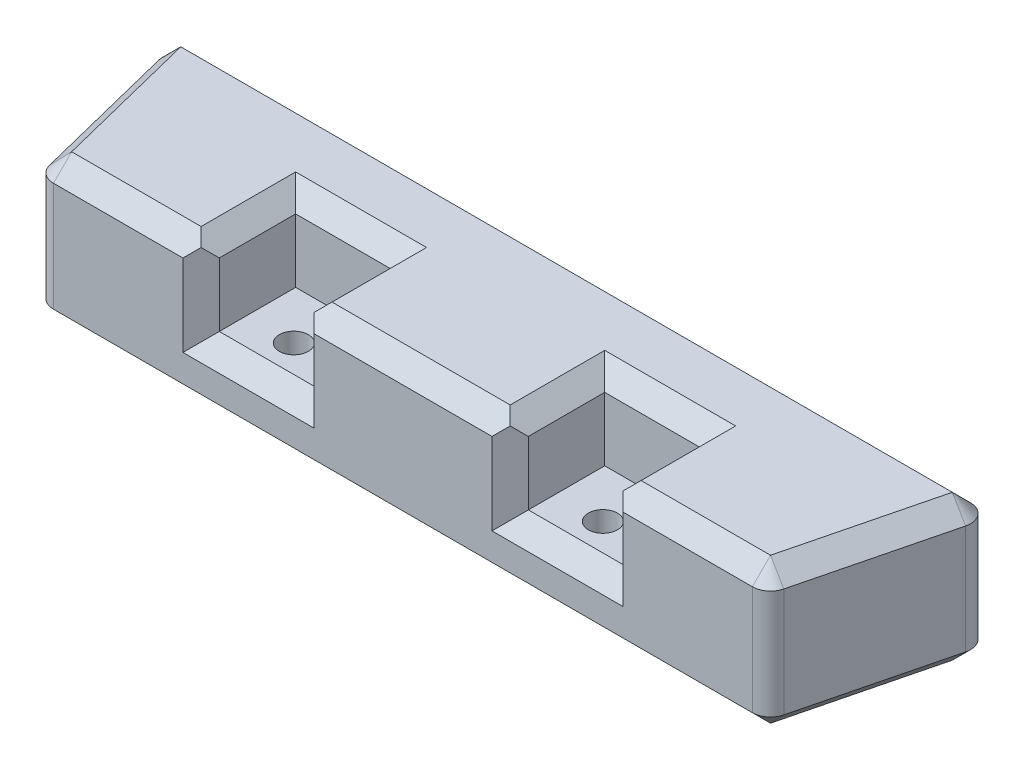
SolidWorks part; units mm, degrees
material "Liga 1060"
ref_plane "Plano frontal" through (0, 0, 0) normal (0, 0, 1) x (1, 0, 0)
ref_plane "Plano superior" through (0, 0, 0) normal (0, 1, 0) x (1, 0, 0)
ref_plane "Plano direito" through (0, 0, 0) normal (1, 0, 0) x (0, 0, -1)
sketch "Esboço2" plane through (0, 0, 0) normal (0, 1, 0) x (1, 0, 0)
  line L4 (-0.1894, 0.7575) -> (-2.1894, 8.7575)
  line L6 (42.1894, 8.7575) -> (40.1894, 0.7575)
  line L7 (39.2192, 0) -> (0.7808, 0)
  line L8 (-1.2192, 10) -> (41.2192, 10)
  arc A1 (40.1894, 0.7575) -> (39.2192, 0) centre (39.2192, 1) cw
  arc A2 (-0.1894, 0.7575) -> (0.7808, 0) centre (0.7808, 1) ccw
  arc A5 (42.1894, 8.7575) -> (41.2192, 10) centre (41.2192, 9) ccw
  arc A6 (-2.1894, 8.7575) -> (-1.2192, 10) centre (-1.2192, 9) cw
  point P2 (20, 10)
  point P6 (20, 0)
  point P7 (42.5, 10)
  point P10 (40, 0)
  point P13 (0, 0)
  point P18 (-2.5, 10)
  dimension "D4" = 1
  dimension "D5" = 45
  dimension "D2" = 10
  dimension "D3" = 1
  dimension "D1" = 40
extrude "Ressalto-extrusão2" add sketch "Esboço2" along normal blind 8
sketch "Esboço4" plane through (0, 8, 0) normal (0, 1, 0) x (1, 0, 0)
  line L0 (20, 0) -> (20, 2.6) construction
  line L1 (0.7808, 0) -> (39.2192, 0) construction
  line L2 (11.5, 2.6) -> (28.5, 2.6) construction
  line L4 (25.9, 0) -> (31.1, 0)
  line L5 (25.9, 0) -> (25.9, 5.2)
  line L6 (25.9, 5.2) -> (31.1, 5.2)
  line L7 (31.1, 0) -> (31.1, 5.2)
  line L8 (25.9, 0) -> (31.1, 5.2) construction
  line L9 (25.9, 5.2) -> (31.1, 0) construction
  line L10 (14.1, 0) -> (8.9, 0)
  line L11 (14.1, 0) -> (14.1, 5.2)
  line L12 (14.1, 5.2) -> (8.9, 5.2)
  line L13 (8.9, 0) -> (8.9, 5.2)
  line L14 (14.1, 0) -> (8.9, 5.2) construction
  line L15 (14.1, 5.2) -> (8.9, 0) construction
  point P7 (20, 2.6)
  dimension "D1" = 17
  dimension "D2" = 2.6
  dimension "D3" = 5.2
  dimension "D4" = 5.2
extrude "Corte-extrusão1" cut sketch "Esboço4" against normal offset from surface (4.5 mm away) 3.5 up to face at (20, 0, -4.8962)
chamfer "Chanfro1" distance 1 angle 45 16 edges at (14.1, 8, -2.6) (11.5, 8, -5.2) (8.9, 8, -2.6) (4.8404, 8, 0) (0.1654, 8, -0.2118) (-1.1894, 8, -4.7575) (41.1894, 8, -4.7575) (39.8346, 8, -0.2118) (35.1596, 8, 0) (31.1, 8, -2.6) (28.5, 8, -5.2) (25.9, 8, -2.6) (20, 8, 0) (20, 8, -10) (-2.0074, 8, -9.6154) (42.0074, 8, -9.6154)
chamfer "Chanfro2" distance 1 angle 45 14 edges at (0.1654, 0, -0.2118) (-1.1894, 0, -4.7575) (41.1894, 0, -4.7575) (39.8346, 0, -0.2118) (20, 0, 0) (31.1, 5.25, 0) (28.5, 3.5, 0) (25.9, 5.25, 0) (14.1, 5.25, 0) (11.5, 3.5, 0) (8.9, 5.25, 0) (20, 0, -10) (-2.0074, 0, -9.6154) (42.0074, 0, -9.6154)
sketch "Esboço5" plane through (0, 3.5, 0) normal (0, 1, 0) x (1, 0, 0)
  line L0 (11.5, 2.5) -> (11.5, 0) construction
  line L1 (11.5, 2.5) -> (14.1, 2.5) construction
  line L2 (14.1, 5.2) -> (14.1, 1) construction
  line L3 (15.1, 0) -> (7.9, 0) construction
  line L4 (32.1, 0) -> (24.9, 0) construction
  line L5 (31.1, 1) -> (31.1, 5.2) construction
  point P0 (11.5, 2.5)
  point P1 (28.5, 2.5)
  dimension "D1" = 2.5
  dimension "D2" = 2.6
  dimension "D3" = 2.5
  dimension "D4" = 2.6
hole_wizard "Furo roscado de M21" positions "3DSketch1" profile "Esboço6" tap size "M2" standard "ISO" end condition through all
sketch3d "3DSketch1"
  point P0 (28.5, 3.5, -2.5)
  point P3 (11.5, 3.5, -2.5)
sketch "Esboço6" plane through (28.5, 3.5, -2.5) normal (1, 0, 0) x (0, 0, 1)
  line L0 (0, 0) -> (0, 3.5)
  line L1 (0, 3.5) -> (0.8, 3.5)
  line L2 (0.8, 3.5) -> (0.8, 0)
  line L5 (0.8, 0) -> (0, 0)
  line L11 (0, -6.35) -> (0, 107.95) construction
  dimension "Thru Tap Drill Dia." = 1.6
  dimension "Thru Tap Drill Depth" = 3.5
cosmetic thread "Rosca de furo1" parameters "D2"=2
cosmetic thread "Rosca de furo2" parameters "D2"=2
